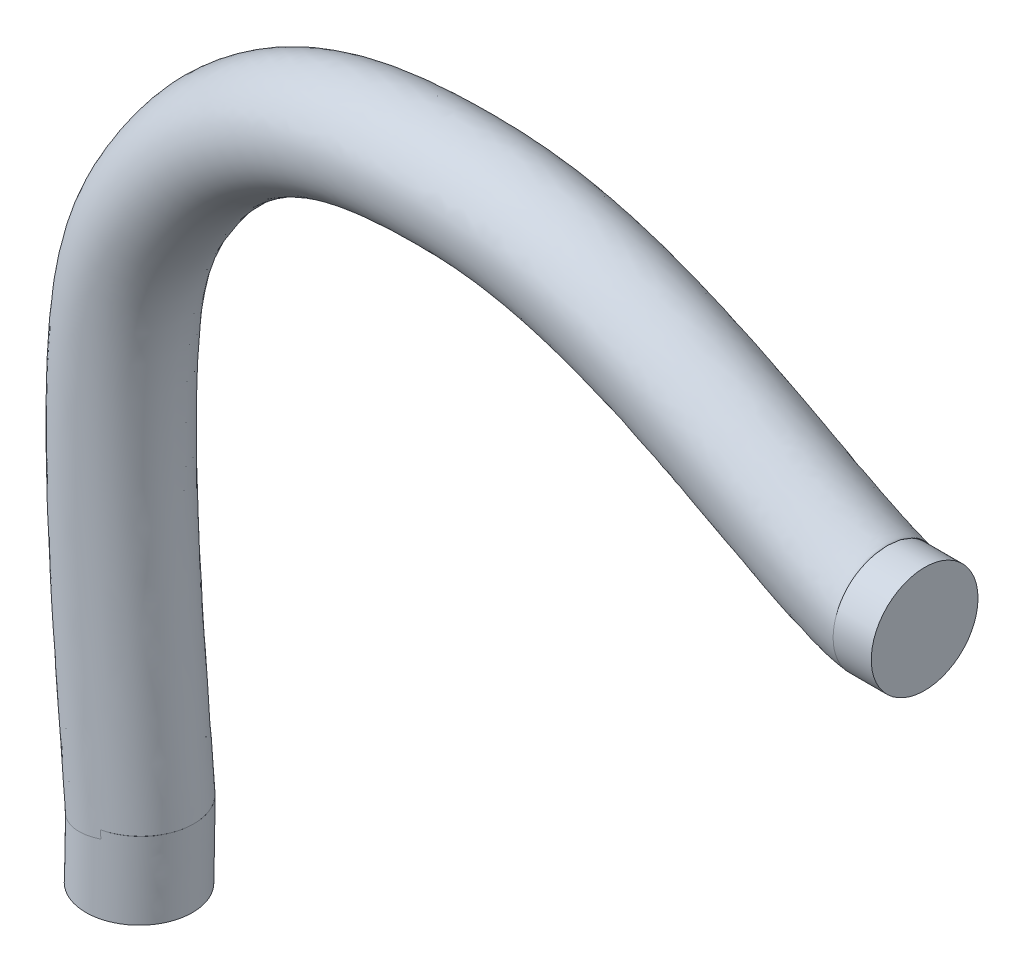
SolidWorks part; units mm, degrees
ref_plane "Front Plane" through (0, 0, 0) normal (0, 0, 1) x (1, 0, 0)
ref_plane "Top Plane" through (0, 0, 0) normal (0, 1, 0) x (1, 0, 0)
ref_plane "Right Plane" through (0, 0, 0) normal (1, 0, 0) x (0, 0, -1)
sketch "Sketch1" plane through (0, 0, 0) normal (1, 0, 0) x (0, 0, -1)
  circle A0 centre (0, 0) radius 7
  dimension "D1" = 14
extrude "Boss-Extrude1" add sketch "Sketch1" along normal blind 5
sketch "Sketch2" plane through (-26.0455, -145.9192, -125.6891) normal (0, 0, 1) x (1, 0, 0)
  spline S0 degree 3 poles (26.0455, 138.9192) (16.1626, 139.8628) (-6.5178, 158.6034) (-40.0487, 159.5302) (-55.5232, 156.4048) (-69.9777, 127.5932) (-65.9095, 88.7683) (-64.9348, 75.7305) knots 0 0 0 0 0.471399 0.556061 0.814335 0.861958 1 1 1 1
  spline S1 degree 3 poles (-66.613, 120.5288) (-65.3145, 94.8745) (-63.3591, 38.2918) (-67.2525, -11.0272) (-69.3826, -58.1494) knots 0.009976 0.009976 0.009976 0.009976 0.240703 0.469301 0.469301 0.469301 0.469301 construction
sketch "Sketch3" plane through (0, 0, 0) normal (0, 0, 1) x (1, 0, 0)
  spline S0 degree 3 poles (-333.0467, 935.9051) (95.9754, -195.3874) (21.4761, 11.1906) (-66.0942, 13.611) (-81.5686, 10.4855) (-108.7995, -43.7927) (-29.5842, -340.862) (-307.865, 905.8762) knots -1.312406 -1.312406 -1.312406 -1.312406 0.471399 0.556061 0.814335 0.861958 1.392399 1.392399 1.392399 1.392399 only from (0, -7) to (-90.9802, -70.1887) construction
  spline S1 degree 3 poles (0, -7) (-9.8828, -6.0564) (-32.5633, 12.6842) (-66.0942, 13.611) (-81.5686, 10.4855) (-96.0231, -18.326) (-91.9549, -57.1509) (-90.9802, -70.1887) knots 0 0 0 0 0.471399 0.556061 0.814335 0.861958 1 1 1 1
sweep "Sweep1" add profiles "Sketch1<2>" path "Sketch3"
sketch "Sketch1<2>" plane through (0, 0, 0) normal (1, 0, 0) x (0, 0, -1) same geometry as "Sketch1"
ref_plane "Plane1" through (0, -70.1662, 1.257) normal (0, -0.9998, 0.0179) x (-1, 0, 0)
sketch "Sketch4" plane through (0, -70.1662, 1.257) normal (0, -0.9998, 0.0179) x (-1, 0, 0)
  ellipse E0 centre (97.8796, 1.2784) end of major axis (98.6069, 8.2405) minor radius 6.8982 construction
  ellipse E1 centre (97.8796, 1.2784) end of major axis (98.6069, 8.2405) minor radius 6.8982
extrude "Boss-Extrude2" add sketch "Sketch4" along normal blind 10
